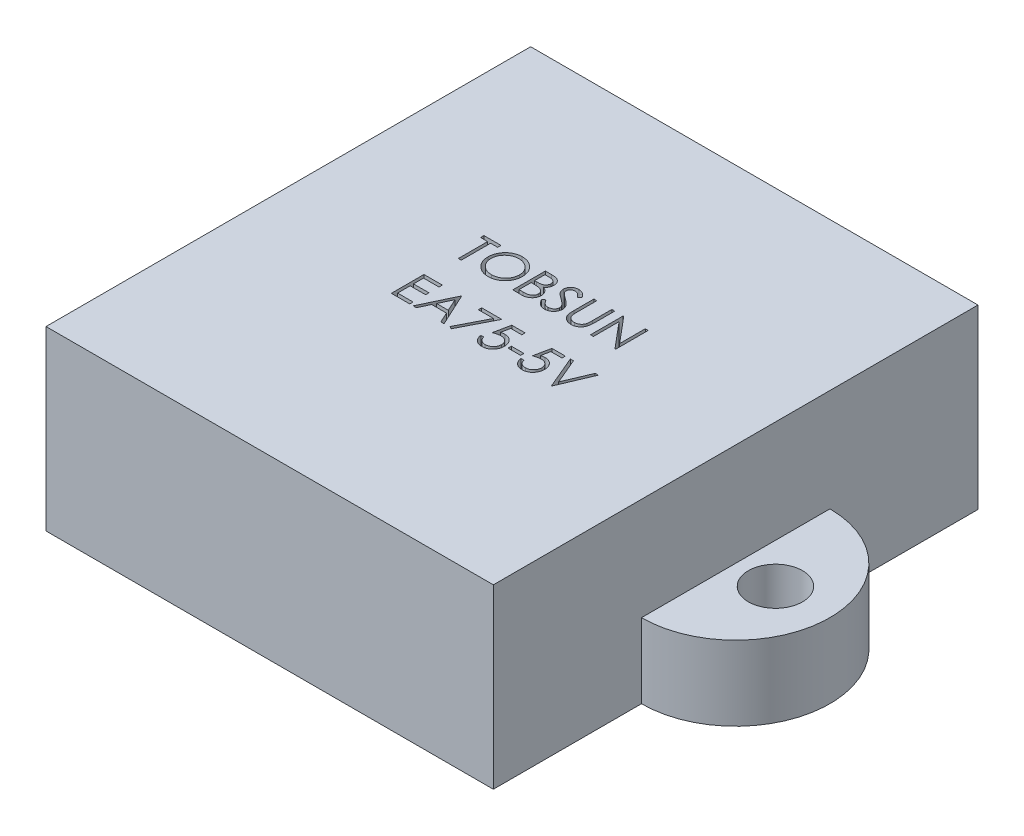
SolidWorks part; units mm, degrees
ref_plane "Front Plane" through (0, 0, 0) normal (0, 0, 1) x (1, 0, 0)
ref_plane "Top Plane" through (0, 0, 0) normal (0, 1, 0) x (1, 0, 0)
ref_plane "Right Plane" through (0, 0, 0) normal (1, 0, 0) x (0, 0, -1)
sketch "Sketch1" plane through (0, 0, 0) normal (0, 1, 0) x (1, 0, 0)
  line L0 (0, 0) -> (0, -26) construction
  line L1 (-24, -26) -> (24, -26)
  line L2 (-24, -26) -> (-24, 26)
  line L3 (-24, 26) -> (24, 26)
  line L4 (24, -26) -> (24, 26)
  line L5 (-24, -26) -> (24, 26) construction
  line L6 (-24, 26) -> (24, -26) construction
  arc A0 (24, 10.1108) -> (24, -10.1108) centre (24, 0) cw
  arc A1 (-24, 10.1108) -> (-24, -10.1108) centre (-24, 0) ccw
  circle A2 centre (28.2683, 0) radius 2.9038
  circle A3 centre (-28.2683, 0) radius 2.9038
  point P0 (0, 0)
extrude "Boss-Extrude1" add sketch "Sketch1" along normal blind 19 contours L1 L4 L3 L2 region at (0, 0, 0)
extrude "Boss-Extrude2" add sketch "Sketch1<3>" along normal blind 8 contours L2 A1 A3 | A0 L4 A2 region at (-33.8847, 0, 0) region at (24.2261, 0, 0)
sketch "Sketch1<3>" plane through (0, 0, 0) normal (0, 1, 0) x (1, 0, 0) same geometry as "Sketch1"
sketch "Sketch2" plane through (0, 19, 0) normal (0, 1, 0) x (1, 0, 0)
  text T0 "TOBSUN\r\nEA75-5V"
extrude "Cut-Extrude1" cut sketch "Sketch2" against normal blind 5.08
